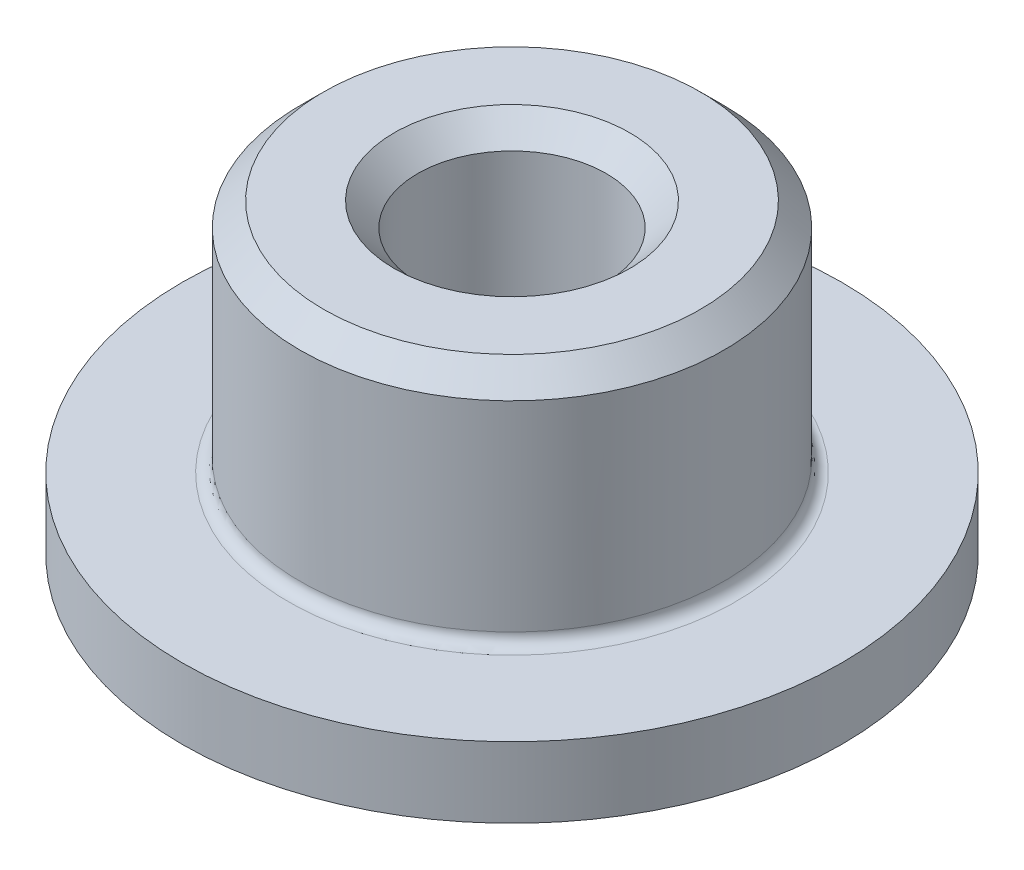
SolidWorks part; units mm, degrees
material "PTFE (general)"
ref_plane "Front Plane" through (0, 0, 0) normal (0, 0, 1) x (1, 0, 0)
ref_plane "Top Plane" through (0, 0, 0) normal (0, 1, 0) x (1, 0, 0)
ref_plane "Right Plane" through (0, 0, 0) normal (1, 0, 0) x (0, 0, -1)
sketch "Sketch1" plane through (0, 0, 0) normal (0, 1, 0) x (1, 0, 0)
  circle A0 centre (0, 0) radius 2
  circle A1 centre (0, 0) radius 4.5
  dimension "D1" = 4
  dimension "D2" = 9
extrude "Boss-Extrude1" add sketch "Sketch1" along normal blind 5
sketch "Sketch2" plane through (0, 0, 0) normal (0, -1, 0) x (1, 0, 0)
  circle A0 centre (0, 0) radius 2 construction
  circle A1 centre (0, 0) radius 2
  circle A2 centre (0, 0) radius 4.5 construction
  circle A3 centre (0, 0) radius 4.5 construction
  circle A4 centre (0, 0) radius 7
  dimension "D1" = 2.5
extrude "Boss-Extrude2" add sketch "Sketch2" along normal blind 1.5
chamfer "Chamfer1" distance 0.5 angle 45 1 edges at (0, 5, 4.5)
fillet "Fillet1" radius 0.25 1 edges at (0, 0, 4.5)
chamfer "Chamfer2" distance 0.5 angle 45 2 edges at (0, 5, 2) (0, -1.5, -2)
